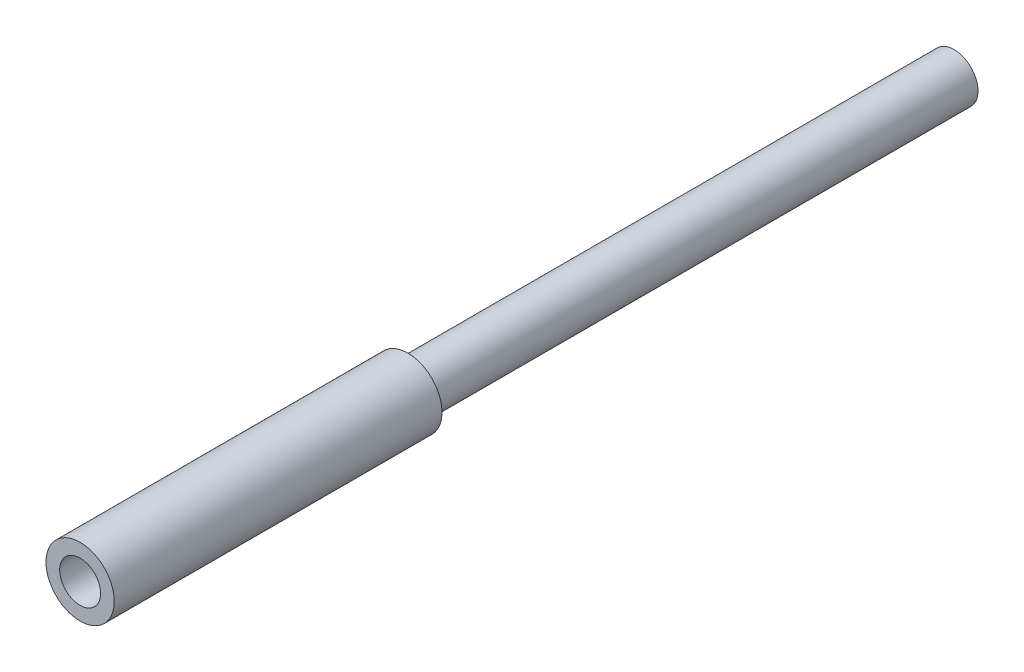
SolidWorks part; units mm, degrees
ref_plane "Front Plane" through (0, 0, 0) normal (0, 0, 1) x (1, 0, 0)
ref_plane "Top Plane" through (0, 0, 0) normal (0, 1, 0) x (1, 0, 0)
ref_plane "Right Plane" through (0, 0, 0) normal (1, 0, 0) x (0, 0, -1)
sketch "Sketch1" plane through (0, 0, 0) normal (0, 0, 1) x (1, 0, 0)
  circle A0 centre (0, 0) radius 7.9375
  dimension "D1" = 15.875
extrude "Boss-Extrude1" add sketch "Sketch1" along normal blind 76.2
sketch "Sketch3" plane through (0, 0, 76.2) normal (0, 0, 1) x (1, 0, 0)
  circle A0 centre (0, 0) radius 4.7625
  dimension "D1" = 9.525
extrude "Cut-Extrude2" cut sketch "Sketch3" against normal blind 63.5
sketch "Sketch4" plane through (0, 0, 0) normal (0, 0, -1) x (-1, 0, 0)
  circle A0 centre (0, 0) radius 5.5626
  dimension "D1" = 11.1252
extrude "Boss-Extrude2" add sketch "Sketch4" along normal blind 127
fillet "Fillet1" radius 0.254 1 edges at (-5.5626, 0, 0)
